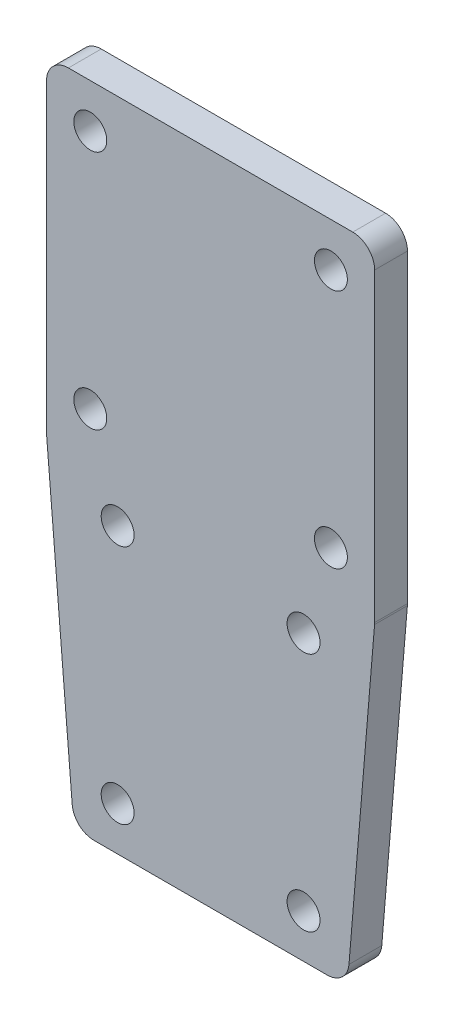
SolidWorks part; units mm, degrees
material "Thornel Mat VMA"
ref_plane "前视基准面" through (0, 0, 0) normal (0, 0, 1) x (1, 0, 0)
ref_plane "上视基准面" through (0, 0, 0) normal (0, 1, 0) x (1, 0, 0)
ref_plane "右视基准面" through (0, 0, 0) normal (1, 0, 0) x (0, 0, -1)
sketch "草图1" plane through (0, 0, 0) normal (0, 0, 1) x (1, 0, 0)
  line L1 (-15, -15) -> (15, -15)
  line L2 (-15, -15) -> (-15, 15)
  line L3 (-15, 15) -> (15, 15)
  line L4 (15, -15) -> (15, 15)
  line L5 (0, 15) -> (0, -15) construction
  line L6 (-15, 0) -> (15, 0) construction
  line L7 (-12.5, -45) -> (12.5, -45)
  line L8 (-12.5, -45) -> (-12.5, -15)
  line L9 (-12.5, -15) -> (12.5, -15)
  line L10 (12.5, -45) -> (12.5, -15)
  line L11 (0, -15) -> (0, -45) construction
  line L12 (-12.5, -30) -> (12.5, -30) construction
  point P0 (0, 0)
  point P4 (0, -30)
  dimension "D1" = 30
  dimension "D2" = 30
  dimension "D3" = 30
  dimension "D4" = 25
extrude "凸台-拉伸1" add sketch "草图1" along normal mid plane 3 contours L1 L4 L3 L2 | L7 L10 L1 L8 region at (0, 0, 0) region at (0, -30, 0)
sketch "草图2" plane through (0, 0, 1.5) normal (0, 0, 1) x (1, 0, 0)
  line L0 (-15, -15) -> (-12.5, -45)
  line L1 (-12.5, -45) -> (12.5, -45)
  line L2 (12.5, -45) -> (15, -15)
  line L3 (15, -15) -> (-15, -15)
extrude "凸台-拉伸2" add sketch "草图2" against normal up to surface (3 mm away) up to face at (0, -15, -1.5)
sketch "草图5" plane through (0, 0, -1.5) normal (0, 0, -1) x (-1, 0, 0)
  line L0 (-12.5, -15) -> (12.5, -45) construction
  line L2 (-8.5, -41) -> (8.5, -41) construction
  line L3 (-8.5, -41) -> (-8.5, -19) construction
  line L4 (-8.5, -19) -> (8.5, -19) construction
  line L5 (8.5, -41) -> (8.5, -19) construction
  line L6 (0, -19) -> (0, -41) construction
  line L7 (-8.5, -30) -> (8.5, -30) construction
  line L8 (-12.5, -45) -> (-12.5, -15) construction
  line L9 (12.5, -45) -> (-12.5, -45) construction
  circle A0 centre (-8.5, -19) radius 1.505
  circle A1 centre (8.5, -19) radius 1.505
  circle A2 centre (-8.5, -41) radius 1.505
  circle A3 centre (8.5, -41) radius 1.505
  point P4 (0, -30)
  point P8 (12.5, -40)
  dimension "D2" = 3.01
  dimension "D1" = 4
  dimension "D3" = 30
  dimension "D4" = 4
extrude "切除-拉伸2" cut sketch "草图5" against normal up to surface (3 mm away) up to face at (0, -15, 1.5)
sketch "草图3" plane through (0, 0, -1.5) normal (0, 0, -1) x (-1, 0, 0)
  line L0 (15, -15) -> (15, 15) construction
  line L1 (-11, -11) -> (11, -11) construction
  line L2 (-11, -11) -> (-11, 11) construction
  line L3 (-11, 11) -> (11, 11) construction
  line L4 (11, -11) -> (11, 11) construction
  line L5 (0, 11) -> (0, -11) construction
  line L6 (-11, 0) -> (11, 0) construction
  line L7 (15, 15) -> (-15, 15) construction
  circle A0 centre (-11, 11) radius 1.505
  circle A1 centre (11, 11) radius 1.505
  circle A2 centre (-11, -11) radius 1.505
  circle A3 centre (11, -11) radius 1.505
  point P0 (0, 0)
  dimension "D3" = 3.01
  dimension "D1" = 4
  dimension "D2" = 4
extrude "切除-拉伸1" cut sketch "草图3" against normal up to surface (3 mm away) up to face at (-6.995, -19, 1.5)
fillet "圆角1" radius 2 6 edges at (-15, -15, 0) (-15, 15, 0) (15, 15, 0) (15, -15, 0) (12.5, -45, 0) (-12.5, -45, 0)
